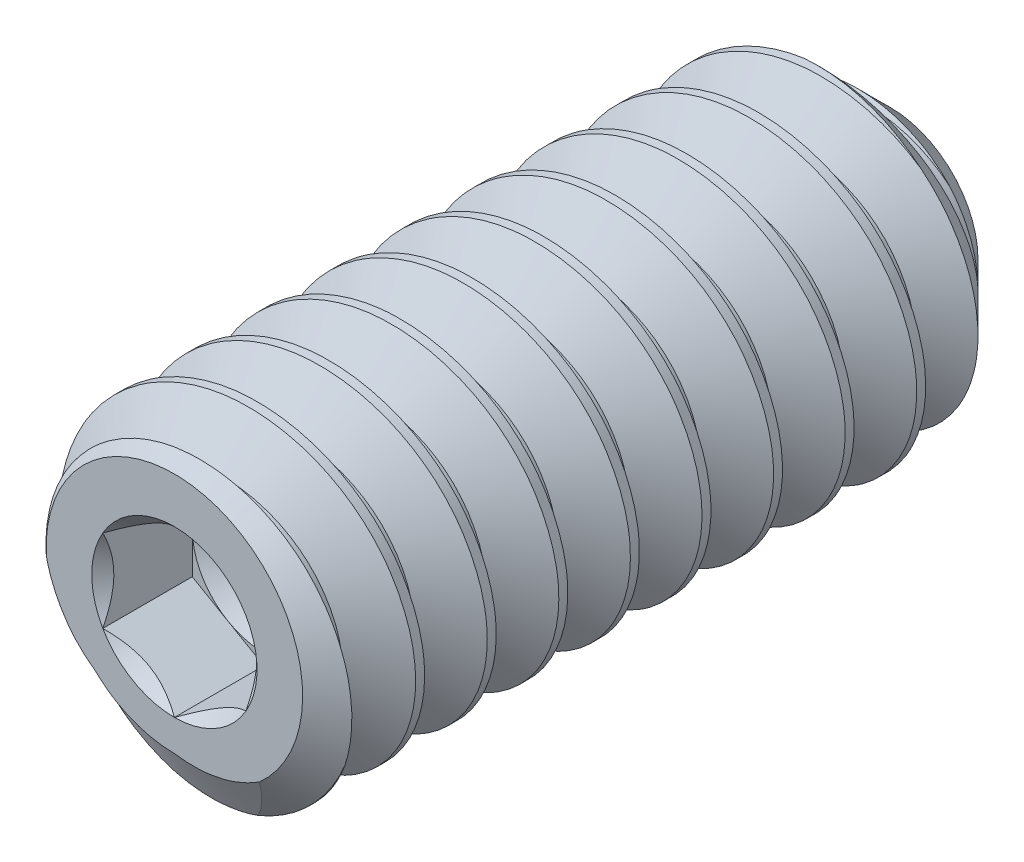
SolidWorks part; units mm, degrees
ref_plane "Front" through (0, 0, 0) normal (0, 0, 1) x (1, 0, 0)
ref_plane "Top" through (0, 0, 0) normal (0, 1, 0) x (1, 0, 0)
ref_plane "Right" through (0, 0, 0) normal (1, 0, 0) x (0, 0, -1)
sketch "Sketch22" plane through (0, 0, 0) normal (1, 0, 0) x (0, 0, -1)
  line L0 (-2.9408, 0) -> (-2.9408, 1.1379)
  line L1 (-2.9408, 1.1379) -> (-2.7416, 1.4224)
  line L2 (-2.7416, 1.4224) -> (2.7662, 1.4224)
  line L3 (2.7662, 1.4224) -> (3.4092, 0.7794)
  line L4 (3.4092, 0.7794) -> (2.9408, 0)
  line L5 (2.9408, 0) -> (-2.9408, 0)
  line L6 (2.9408, 0) -> (3.4092, 0) construction
  line L7 (3.4092, 0) -> (3.4092, 0.7794) construction
  line L8 (3.4092, -0.7794) -> (2.9408, 0) construction
  line L9 (-2.7416, -1.4224) -> (2.7662, -1.4224) construction
  dimension "Dia" = 2.8448
  dimension "Length" = 6.35
  dimension "D3" = 35
  dimension "D5" = 118
  dimension "D6" = 45
  dimension "D7" = 2.2758
revolve "Revolve1" add sketch "Sketch22" angle 360 about L6
ref_plane "Plane1" through (0, 0, -3.4092) normal (0, 0, 1) x (1, 0, 0)
sketch "Sketch27" plane through (0, 0, -3.4092) normal (0, 0, 1) x (1, 0, 0)
  circle A0 centre (0, 0) radius 1.4224 construction
  circle A1 centre (0, 0) radius 1.4224
curve "Helix/Spiral1" pitch 0.635 height 6.985 radius 1.4224 centre (0, 0, -3.4092) axis (0, 0, 1) start towards (0, 1, 0)
sketch "Sketch28" plane through (0, 0, 0) normal (1, 0, 0) x (0, 0, -1)
  line L0 (3.4092, 1.4224) -> (3.9648, 1.4224)
  line L1 (3.9648, 1.4224) -> (3.7267, 1.01)
  line L2 (3.7267, 1.01) -> (3.6473, 1.01)
  line L3 (3.6473, 1.01) -> (3.4092, 1.4224)
  line L4 (3.5282, 1.2162) -> (3.8457, 1.2162) construction
  line L6 (-2.7416, 1.4224) -> (2.7662, 1.4224) construction
  line L7 (3.4092, 1.5646) -> (3.4092, -1.5646) construction
  dimension "D1" = 0.0794
  dimension "D3" = 60
  dimension "D2" = 0.3175
sweep "Cut-Sweep2" cut profiles "Sketch28" path "Helix/Spiral1" align with end faces yes
sketch "Sketch23" plane through (0, 0, 2.9408) normal (0, 0, 1) x (1, 0, 0)
  line L1 (0, 0.7332) -> (-0.635, 0.3666)
  line L2 (-0.635, 0.3666) -> (-0.635, -0.3666)
  line L3 (-0.635, -0.3666) -> (0, -0.7332)
  line L4 (0, -0.7332) -> (0.635, -0.3666)
  line L5 (0.635, -0.3666) -> (0.635, 0.3666)
  line L6 (0.635, 0.3666) -> (0, 0.7332)
  circle A0 centre (0, 0) radius 0.635 construction
  dimension "Hex" = 1.27
extrude "Cut-Extrude10" cut sketch "Sketch23" against normal blind 0.7937
sketch "Sketch24" plane through (0, 0, 2.9408) normal (0, 0, 1) x (1, 0, 0)
  circle A0 centre (0, 0) radius 0.7332
extrude "Cut-Extrude11" cut sketch "Sketch24" against normal through all draft 45
sketch "Sketch26" plane through (0, 0, 2.1471) normal (0, 0, 1) x (1, 0, 0)
  circle A0 centre (0, 0) radius 0.635 construction
  circle A1 centre (0, 0) radius 0.635
extrude "Cut-Extrude12" cut sketch "Sketch26" against normal through all draft 60
sketch "Sketch30" plane through (0, 0, 0) normal (1, 0, 0) x (0, 0, -1)
  line L0 (-2.7416, 1.4224) -> (2.7662, 1.4224) construction
  line L1 (-2.9408, 0) -> (-2.9408, 1.1379) construction
  line L2 (3.4092, 0) -> (3.4092, 0.7794) construction
  line L3 (-2.7416, -1.4224) -> (2.7662, -1.4224) construction
  point P0 (-2.9408, 1.4224)
  point P1 (3.4092, 1.4224)
  point P2 (3.4092, -1.4224)
  point P11 (1.1867, -1.4224)
  dimension "D1" = 2.2225
sketch "Sketch31" plane through (0, 0, 0) normal (1, 0, 0) x (0, 0, -1)
  line L2 (2.9408, 0) -> (3.4092, -0.7794)
  line L3 (3.4092, 0.7794) -> (2.9408, 0)
equation "\"D7@Sketch22\"=\"Dia@Sketch22\"*.8"
equation "\"D1@Sketch28\" = \"D4@Helix/Spiral1\" * .125"
equation "\"D3@Helix/Spiral1\" = \"Length@Sketch22\" + \"D4@Helix/Spiral1\""
equation "\"D1@Sketch30\" = \"D4@Helix/Spiral1\" * 3.5"
equation "\"hex Depth@Cut-Extrude10\" = \"Hex@Sketch23\" * .625"
equation "\"D2@Sketch28\" = \"D4@Helix/Spiral1\" * .5"
